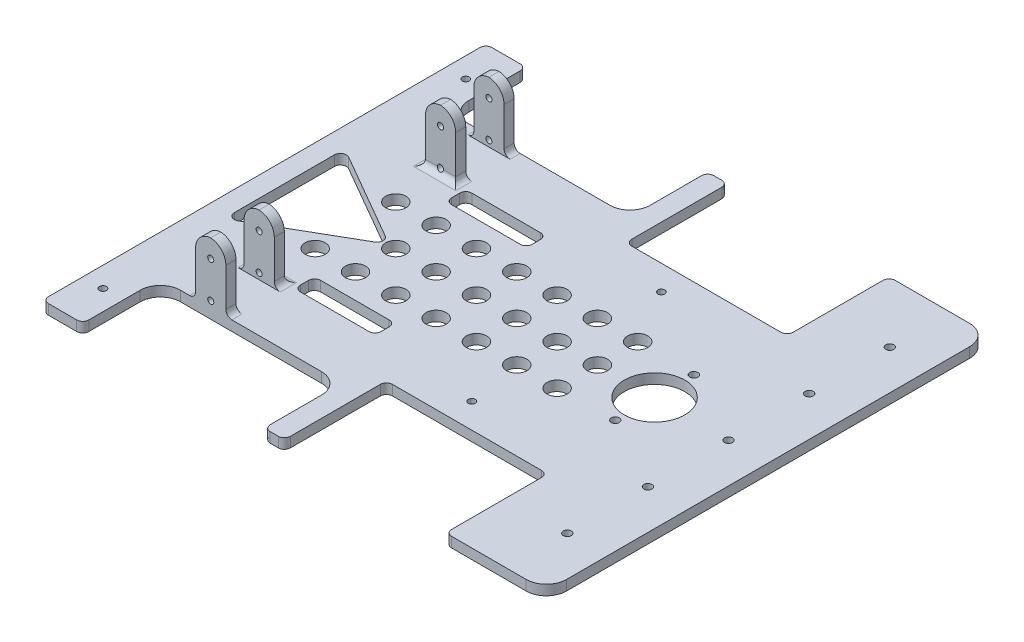
SolidWorks part; units mm, degrees
ref_plane "Front Plane" through (0, 0, 0) normal (0, 0, 1) x (1, 0, 0)
ref_plane "Top Plane" through (0, 0, 0) normal (0, 1, 0) x (1, 0, 0)
ref_plane "Right Plane" through (0, 0, 0) normal (1, 0, 0) x (0, 0, -1)
sketch "Sketch1" plane through (0, 0, 0) normal (0, 1, 0) x (1, 0, 0)
  line L1 (-125, 110) -> (125, 110)
  line L2 (-125, 110) -> (-125, -110)
  line L3 (-125, -110) -> (125, -110)
  line L4 (125, 110) -> (125, -110)
  line L5 (-125, 110) -> (125, -110) construction
  line L6 (-125, -110) -> (125, 110) construction
  point P1 (0, 0)
  dimension "D1" = 250
  dimension "D2" = 220
extrude "Boss-Extrude1" add sketch "Sketch1" along normal mid plane 5
sketch "Sketch2" plane through (0, 0, 0) normal (0, 1, 0) x (1, 0, 0)
  line L0 (0, 110) -> (0, -110) construction
  line L1 (125, 110) -> (-125, 110) construction
  line L2 (-125, -110) -> (125, -110) construction
  line L3 (125, 0) -> (-125, 0) construction
  line L4 (125, -110) -> (125, 110) construction
  line L5 (-125, 110) -> (-125, -110) construction
  line L6 (-115, 90) -> (-115, 0) construction
  line L7 (-115, -90) -> (-115, 0) construction
  line L8 (-125, 110) -> (-125, -110) construction
  line L9 (-115, 90) -> (125, 90) construction
  line L10 (-15, 90) -> (-15, -90) construction
  line L12 (125, -110) -> (125, 110) construction
  line L13 (25, 90) -> (25, -110) construction
  line L15 (-125, -110) -> (125, -110) construction
  circle A0 centre (-115, 90) radius 1.75
  circle A1 centre (-115, -90) radius 1.75
  circle A6 centre (25, 47) radius 1.75
  circle A7 centre (25, -47) radius 1.75
  dimension "D2" = 3.5
  dimension "D3" = 3.5
  dimension "D6" = 3.5
  dimension "D1" = 20
  dimension "D4" = 10
  dimension "D5" = 140
  dimension "D7" = 47
extrude "Link nails" cut sketch "Sketch2" along direction (0, 1, 0) on the side against the normal mid plane 5
sketch "Sketch3" plane through (0, 0, 0) normal (0, 1, 0) x (1, 0, 0)
  line L0 (125, 0) -> (-125, 0) construction
  line L1 (125, -110) -> (125, 110) construction
  line L2 (-125, 110) -> (-125, -110) construction
  line L3 (-105, 110) -> (-105, 71.5023)
  line L4 (125, 110) -> (-125, 110) construction
  line L5 (-105, 71.5023) -> (-15, 71.5023)
  line L6 (-15, 71.5023) -> (-15, 110)
  line L7 (-15, 110) -> (-105, 110)
  line L8 (-15, -71.5023) -> (-15, -110)
  line L9 (-105, -110) -> (-105, -71.5023)
  line L10 (-105, -71.5023) -> (-15, -71.5023)
  line L11 (-15, -110) -> (-105, -110)
  dimension "D1" = 90
  dimension "D2" = 20
extrude "Cut-Extrude2" cut sketch "Sketch3" against normal mid plane 5
fillet "Fillet3" radius 10 4 edges at (-15, 0, 71.5023) (-105, 0, 71.5023) (-105, 0, -71.5023) (-15, 0, -71.5023)
sketch "Sketch4" plane through (0, 0, 0) normal (0, 1, 0) x (1, 0, 0)
  line L0 (125, 0) -> (-125, 0) construction
  line L1 (125, -110) -> (125, 110) construction
  line L2 (-125, 110) -> (-125, -110) construction
  line L6 (68.6574, 19.5) -> (68.6574, 0) construction
  line L7 (68.6574, 0) -> (68.6574, -19.5) construction
  circle A0 centre (68.6574, 0) radius 15
  circle A1 centre (68.6574, 19.5) radius 2
  circle A2 centre (68.6574, -19.5) radius 2
  dimension "D1" = 30
  dimension "D2" = 2
  dimension "D3" = 4
  dimension "D4" = 39
extrude "middle hole" cut sketch "Sketch4" against normal mid plane 5
sketch "Sketch6" plane through (0, 0, 0) normal (0, 1, 0) x (1, 0, 0)
  line L0 (125, 0) -> (-125, 0) construction
  line L1 (125, -110) -> (125, 110) construction
  line L2 (-125, 110) -> (-125, -110) construction
  line L3 (125, -110) -> (125, 110) construction
  circle A0 centre (105.3612, 0) radius 2
  dimension "D1" = 4
  dimension "D2" = 19.6388
extrude "Cut-Extrude4" cut sketch "Sketch6" against normal mid plane 5
pattern_linear "LPattern1" count 3 spacing 40 along (0, 0, -1) of "Cut-Extrude4"
pattern_linear "LPattern2" count 3 spacing 40 along (0, 0, 1) of "Cut-Extrude4"
sketch "Sketch8" plane through (0, 2.5, 0) normal (0, 1, 0) x (1, 0, 0)
  line L0 (-25, -71.5023) -> (-95, -71.5023) construction
  line L1 (-87.5, -71.5023) -> (-72.5, -71.5023)
  line L2 (-87.5, -71.5023) -> (-87.5, -66.5023)
  line L3 (-87.5, -66.5023) -> (-72.5, -66.5023)
  line L4 (-72.5, -71.5023) -> (-72.5, -66.5023)
  line L6 (125, 0) -> (-125, 0) construction
  line L7 (125, -110) -> (125, 110) construction
  line L8 (-125, 110) -> (-125, -110) construction
  line L13 (-125, -47.5023) -> (125, -47.5023) construction
  line L14 (125, -110) -> (125, 110) construction
  line L15 (-80, -66.5023) -> (-80, -47.5023) construction
  line L16 (-80, -57.0023) -> (-125, -57.0023) construction
  line L17 (-72.5, -42.5023) -> (-72.5, -47.5023)
  line L18 (-87.5, -47.5023) -> (-72.5, -47.5023)
  line L19 (-87.5, -42.5023) -> (-87.5, -47.5023)
  line L20 (-87.5, -42.5023) -> (-72.5, -42.5023)
  line L21 (-80, 57.0023) -> (-125, 57.0023) construction
  line L22 (-80, 66.5023) -> (-80, 47.5023) construction
  line L23 (-125, 47.5023) -> (125, 47.5023) construction
  line L24 (-87.5, 42.5023) -> (-72.5, 42.5023)
  line L25 (-87.5, 42.5023) -> (-87.5, 47.5023)
  line L26 (-87.5, 47.5023) -> (-72.5, 47.5023)
  line L27 (-72.5, 42.5023) -> (-72.5, 47.5023)
  line L28 (-72.5, 71.5023) -> (-72.5, 66.5023)
  line L29 (-87.5, 66.5023) -> (-72.5, 66.5023)
  line L30 (-87.5, 71.5023) -> (-87.5, 66.5023)
  line L31 (-87.5, 71.5023) -> (-72.5, 71.5023)
  line L32 (-15, -110) -> (-105, -110) construction
  line L33 (-60, -110) -> (-60, 0) construction
  point P22 (-80, -66.5023)
  point P47 (-80, -71.5023)
  dimension "D1" = 5
  dimension "D3" = 15
  dimension "D4" = 19
  dimension "D5" = 20
  dimension "D2" = 27.5
extrude "Boss-Extrude2" add sketch "Sketch8" along normal blind 30
sketch "Sketch10" plane through (0, 0, 0) normal (0, 1, 0) x (1, 0, 0)
  line L0 (-15, -110) -> (-15, -81.5023) construction
  line L1 (-67.5, -32.5023) -> (-27.5, -32.5023)
  line L2 (-67.5, -32.5023) -> (-67.5, -42.5023)
  line L3 (-67.5, -42.5023) -> (-27.5, -42.5023)
  line L4 (-27.5, -32.5023) -> (-27.5, -42.5023)
  line L5 (-125, 110) -> (-125, -110) construction
  line L6 (-125, 0) -> (125, 0) construction
  line L7 (125, -110) -> (125, 110) construction
  line L8 (-27.5, 32.5023) -> (-27.5, 42.5023)
  line L9 (-67.5, 42.5023) -> (-27.5, 42.5023)
  line L10 (-67.5, 32.5023) -> (-67.5, 42.5023)
  line L11 (-67.5, 32.5023) -> (-27.5, 32.5023)
  line L13 (-72.5, -47.5023) -> (-72.5, -42.5023) construction
  dimension "D1" = 5
  dimension "D3" = 40
  dimension "D4" = 10
extrude "Cut-Extrude6" cut sketch "Sketch10" against normal mid plane 67.5
sketch "Sketch9" plane through (0, 0, 71.5023) normal (0, 0, 1) x (1, 0, 0)
  line L0 (-80, 32.5) -> (-80, -2.5) construction
  line L1 (-87.5, 32.5) -> (-72.5, 32.5) construction
  line L2 (-25, -2.5) -> (-95, -2.5) construction
  line L3 (-25, 2.5) -> (-72.5, 2.5) construction
  circle A0 centre (-80, 23.5) radius 1.5
  circle A1 centre (-80, 5.5) radius 1.5
  dimension "D1" = 3
  dimension "D2" = 3
  dimension "D3" = 3
  dimension "D4" = 18
extrude "Cut-Extrude5" cut sketch "Sketch9" against normal up to surface (143.0046 mm away) up to face at (-70, 8.75, -71.5023)
fillet "Fillet6" radius 8 8 edges at (-87.5, 32.5, 69.0023) (-72.5, 32.5, 69.0023) (-72.5, 32.5, -69.0023) (-87.5, 32.5, -69.0023) (-87.5, 32.5, -45.0023) (-72.5, 32.5, -45.0023) (-72.5, 32.5, 45.0023) (-87.5, 32.5, 45.0023)
fillet "Fillet7" radius 10 2 edges at (125, 0, 110) (125, 0, -110)
fillet "Fillet8" radius 3 8 edges at (-67.5, 0, 32.5023) (-67.5, 0, 42.5023) (-67.5, 0, -42.5023) (-67.5, 0, -32.5023) (-27.5, 0, -32.5023) (-27.5, 0, 32.5023) (-27.5, 0, -42.5023) (-27.5, 0, 42.5023)
sketch "Sketch11" plane through (0, 0, 0) normal (0, 1, 0) x (1, 0, 0)
  line L0 (-125, 0) -> (125, 0) construction
  line L1 (-125, 110) -> (-125, -110) construction
  line L2 (125, -100) -> (125, 100) construction
  line L3 (-63.0385, 0) -> (-115, 30)
  line L4 (-115, 30) -> (-115, -30)
  line L5 (-115, -30) -> (-63.0385, 0)
  line L6 (-115, 90) -> (-115, -90) construction
  dimension "D1" = 60
extrude "Cut-Extrude7" cut sketch "Sketch11" against normal mid plane 10
fillet "Fillet9" radius 3 3 edges at (-115, 0, 30) (-115, 0, -30) (-63.0385, 0, 0)
sketch "Sketch12" plane through (0, 0, 0) normal (0, 1, 0) x (1, 0, 0)
  line L0 (-115, 90) -> (-115, -90) construction
fillet "Fillet10" radius 3 10 edges at (-87.5, 2.5, -45.0023) (-87.5, 2.5, -69.0023) (-80, 2.5, -42.5023) (-80, 2.5, 42.5023) (-87.5, 2.5, 45.0023) (-72.5, 2.5, 45.0023) (-72.5, 2.5, -69.0023) (-72.5, 2.5, -45.0023) (-87.5, 2.5, 69.0023) (-72.5, 2.5, 69.0023)
sketch "Sketch14" plane through (0, 0, 0) normal (0, 1, 0) x (1, 0, 0)
  line L0 (75, -110) -> (75, -59.3668)
  line L1 (-15, -110) -> (115, -110) construction
  line L2 (75, -59.3668) -> (-5, -59.3668)
  line L3 (-5, -59.3668) -> (-5, -110)
  line L4 (-5, -110) -> (75, -110)
  line L5 (125, 0) -> (-125, 0) construction
  line L6 (125, -100) -> (125, 100) construction
  line L7 (-125, 110) -> (-125, -110) construction
  line L8 (-5, 110) -> (75, 110)
  line L9 (-5, 59.3668) -> (-5, 110)
  line L10 (75, 59.3668) -> (-5, 59.3668)
  line L11 (75, 110) -> (75, 59.3668)
  line L12 (-15, -110) -> (-15, -81.5023) construction
  dimension "D1" = 50
  dimension "D2" = 10
extrude "Cut-Extrude8" cut sketch "Sketch14" against normal mid plane 10
fillet "Fillet11" radius 3 14 edges at (-125, 0, 110) (-105, 0, 110) (-15, 0, 110) (-5, 0, 110) (-5, 0, 59.3668) (75, 0, 110) (75, 0, 59.3668) (75, 0, -110) (75, 0, -59.3668) (-5, 0, -59.3668) (-5, 0, -110) (-15, 0, -110) (-105, 0, -110) (-125, 0, -110)
sketch "Sketch15" plane through (0, 0, 0) normal (0, 1, 0) x (1, 0, 0)
  line L0 (-125, 27.8038) -> (125, 27.8038) construction
  line L1 (-125, 107) -> (-125, -107) construction
  line L2 (125, -100) -> (125, 100) construction
  arc A0 (-110.5, 27.4019) -> (-115, 24.8038) centre (-112, 24.8038) ccw construction
  circle A1 centre (40.4983, 19.8038) radius 5
  point P11 (0, 0)
  dimension "D1" = 10
  dimension "D2" = 8
extrude "Cut-Extrude9" cut sketch "Sketch15" against normal mid plane 10
pattern_linear "LPattern3" count 7 spacing 20 along (-1, 0, 0) count 3 spacing 20 along (0, 0, 1) of "Cut-Extrude9"
equation "\"carW\"= 22cm"
equation "\"carL\"= 25cm"
equation "\"D1@Sketch1\"=\"carL\""
equation "\"D2@Sketch1\"=\"carW\""
equation "\"carT\"= .5cm'car thickness"
equation "\"D1@Boss-Extrude1\"=\"carT\""
equation "\"linkNialDim\"= 0.35cm"
equation "\"D2@Sketch2\"=\"linkNialDim\""
equation "\"D3@Sketch2\"=\"linkNialDim\""
equation "\"D1@Sketch8\"=\"carT\""
equation "\"D6@Sketch2\"=\"linkNialDim\""
